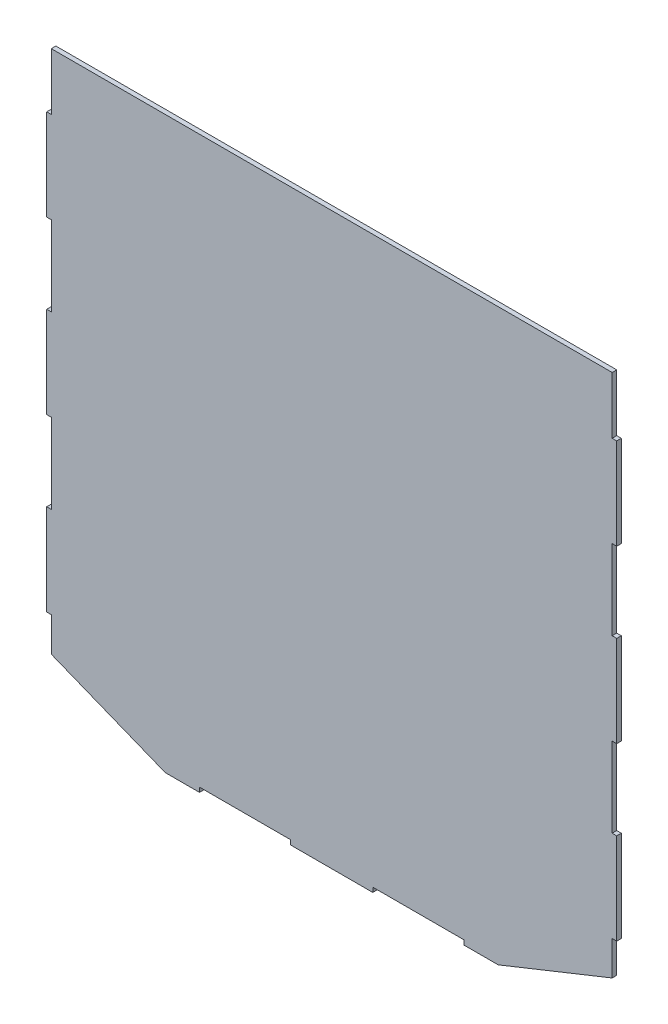
SolidWorks part; units mm, degrees
material "ABS PC"
ref_plane "Спереди" through (0, 0, 0) normal (0, 0, 1) x (1, 0, 0)
ref_plane "Сверху" through (0, 0, 0) normal (0, 1, 0) x (1, 0, 0)
ref_plane "Справа" through (0, 0, 0) normal (1, 0, 0) x (0, 0, -1)
sketch "Sketch1" plane through (0, 0, 0) normal (0, 0, 1) x (1, 0, 0)
  line L0 (-123, 35) -> (-123, 20)
  line L1 (-123, 250) -> (123, 250)
  line L2 (0, 250) -> (0, 0) construction
  line L3 (-73, 0) -> (-58, 0)
  line L4 (-123, 35) -> (-125, 35)
  line L5 (-125, 35) -> (-125, 75)
  line L6 (-125, 75) -> (-123, 75)
  line L7 (-123, 110) -> (-125, 110)
  line L8 (-125, 110) -> (-125, 150)
  line L9 (-125, 150) -> (-123, 150)
  line L10 (-123, 185) -> (-125, 185)
  line L11 (-125, 185) -> (-125, 225)
  line L12 (-125, 225) -> (-123, 225)
  line L13 (-123, 75) -> (-123, 110)
  line L14 (-123, 150) -> (-123, 185)
  line L15 (-123, 225) -> (-123, 250)
  line L16 (-58, 0) -> (-58, 2)
  line L17 (-58, 2) -> (-18, 2)
  line L18 (-18, 2) -> (-18, 0)
  line L19 (-18, 0) -> (18, 0)
  line L20 (123, 20) -> (73, 0)
  line L21 (18, 2) -> (18, 0)
  line L22 (58, 2) -> (18, 2)
  line L23 (58, 0) -> (58, 2)
  line L24 (123, 225) -> (123, 250)
  line L25 (123, 150) -> (123, 185)
  line L26 (123, 75) -> (123, 110)
  line L27 (125, 225) -> (123, 225)
  line L28 (125, 185) -> (125, 225)
  line L29 (-123, 20) -> (-73, 0)
  line L30 (123, 185) -> (125, 185)
  line L31 (125, 150) -> (123, 150)
  line L32 (125, 110) -> (125, 150)
  line L33 (123, 110) -> (125, 110)
  line L34 (125, 75) -> (123, 75)
  line L35 (125, 35) -> (125, 75)
  line L36 (123, 35) -> (125, 35)
  line L37 (73, 0) -> (58, 0)
  line L38 (123, 35) -> (123, 20)
  dimension "D1" = 123
  dimension "D2" = 250
  dimension "D3" = 20
  dimension "D4" = 25
  dimension "D5" = 100
  dimension "D6" = 2
  dimension "D7" = 40
  dimension "D8" = 175
  dimension "D9" = 50
  dimension "D10" = 65
extrude "Boss-Extrude1" add sketch "Sketch1" along normal blind 2
